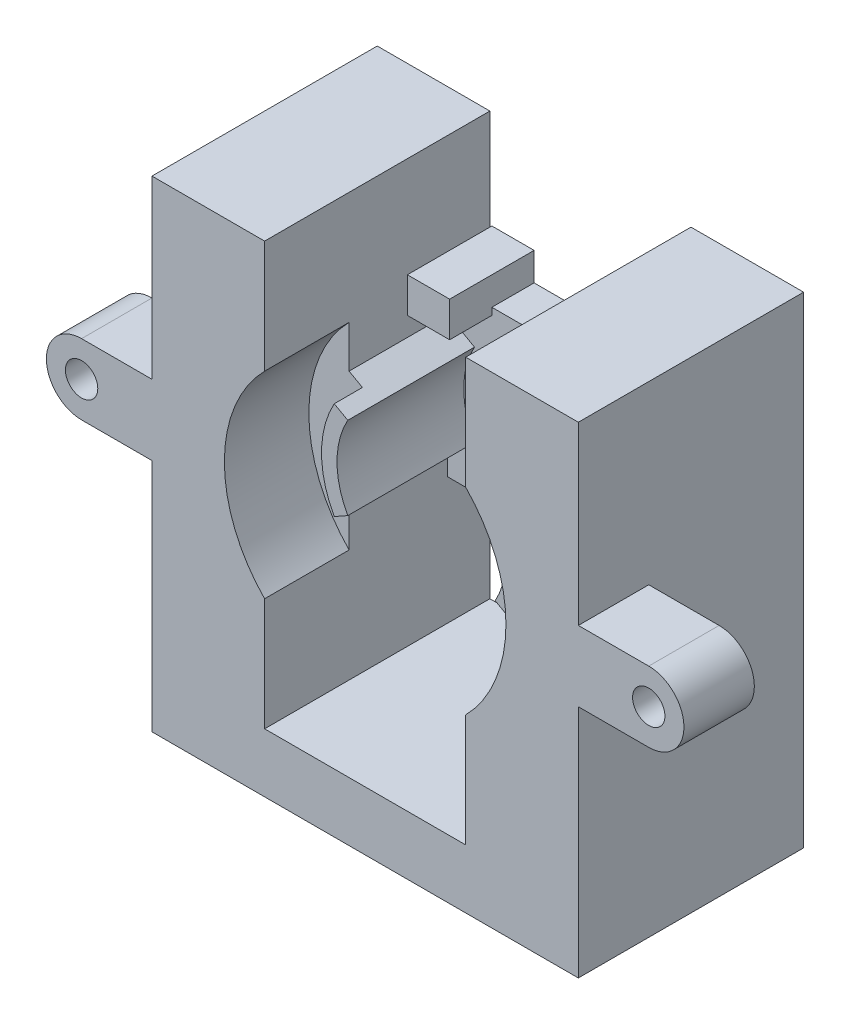
SolidWorks part; units mm, degrees
ref_plane "前视基准面" through (0, 0, 0) normal (0, 0, 1) x (1, 0, 0)
ref_plane "上视基准面" through (0, 0, 0) normal (0, 1, 0) x (1, 0, 0)
ref_plane "右视基准面" through (0, 0, 0) normal (1, 0, 0) x (0, 0, -1)
sketch "草图1" plane through (0, 0, 0) normal (0, 0, 1) x (1, 0, 0)
  line L0 (7.1414, 7) -> (7.1414, 15)
  line L1 (7.1414, 15) -> (15.1414, 15)
  line L2 (15.1414, 15) -> (15.1414, -19.186)
  line L3 (7.1414, -7) -> (7.1414, -15)
  line L4 (0, -293.0825) -> (0, 14343.5987) construction
  line L5 (4, 0) -> (4, -15) construction
  line L6 (4, -15) -> (7.1414, -15)
  line L7 (-4, 0) -> (-4, -15) construction
  line L8 (-4, -15) -> (-7.1414, -15)
  line L9 (-7.1414, -7) -> (-7.1414, -15)
  line L10 (-15.1414, 15) -> (-15.1414, -19.186)
  line L11 (-7.1414, 15) -> (-15.1414, 15)
  line L12 (-7.1414, 7) -> (-7.1414, 15)
  line L13 (-15.1414, -19.186) -> (15.1414, -19.186)
  line L14 (-4, -15) -> (4, -15)
  line L15 (7.1414, 7) -> (7.1414, 4)
  line L16 (7.1414, 4) -> (5.2348, 2.9321)
  line L17 (-1000, 0) -> (49000, 0) construction
  line L18 (7.1414, -4) -> (5.2348, -2.9321)
  line L19 (7.1414, -7) -> (7.1414, -4)
  line L20 (-7.1414, -7) -> (-7.1414, -4)
  line L21 (-7.1414, -4) -> (-5.2348, -2.9321)
  line L22 (-7.1414, 4) -> (-5.2348, 2.9321)
  line L23 (-7.1414, 7) -> (-7.1414, 4)
  line L24 (20.1414, 2.5) -> (15.1414, 2.5)
  line L25 (20.1414, -2.5) -> (15.1414, -2.5)
  line L26 (-20.1414, -2.5) -> (-15.1414, -2.5)
  line L27 (-20.1414, 2.5) -> (-15.1414, 2.5)
  line L28 (-7.1414, 6) -> (7.1414, 6)
  line L29 (-7.1414, -6) -> (7.1414, -6)
  circle A0 centre (0, 0) radius 4 construction
  circle A1 centre (0, 0) radius 10 construction
  circle A2 centre (0, 0) radius 2.6
  arc A3 (7.1414, 7) -> (7.1414, -7) centre (0, 0) cw
  arc A4 (-7.1414, 7) -> (-7.1414, -7) centre (0, 0) ccw
  circle A6 centre (0, 0) radius 6 construction
  circle A7 centre (0, 0) radius 7.1 construction
  arc A8 (5.2348, 2.9321) -> (5.2348, -2.9321) centre (0, 0) cw
  arc A9 (6.1945, 3.4696) -> (6.1945, -3.4696) centre (0, 0) cw
  arc A10 (-5.2348, 2.9321) -> (-5.2348, -2.9321) centre (0, 0) ccw
  arc A11 (-6.1945, 3.4696) -> (-6.1945, -3.4696) centre (0, 0) ccw
  circle A12 centre (20.1414, 0) radius 1.15
  circle A13 centre (20.1414, 0) radius 2.5 construction
  arc A14 (20.1414, 2.5) -> (20.1414, -2.5) centre (20.1414, 0) cw
  circle A15 centre (-20.1414, 0) radius 1.15
  arc A16 (-20.1414, 2.5) -> (-20.1414, -2.5) centre (-20.1414, 0) ccw
  dimension "D2" = 5.2
  dimension "D3" = 8
  dimension "D4" = 10
  dimension "D9" = 14.2
  dimension "D10" = 12
  dimension "D12" = 2.3
  dimension "D13" = 5
  dimension "D1" = 15
  dimension "D5" = 8
  dimension "D6" = 8
  dimension "D7" = 34.186
  dimension "D8" = 8
  dimension "D11" = 3
  dimension "D14" = 5
  dimension "D15" = 6
extrude "凸台-拉伸2" add sketch "草图1" along normal blind 16 contours A4 L12 L11 L10 L13 L2 L1 L0 A3 L3 L6 L14 L8 L9 | A11 L22 L23 A4 L20 L21 | L22 A11 L21 A10 | A9 L16 A8 L18 | L16 A9 L18 L19 A3 L15 region at (8.1661, 0, 0) region at (7.5981, 11, 0) region at (-8.1661, 0, 0) region at (6.2838, 0, 0) region at (-6.2838, 0, 0)
extrude "凸台-拉伸3" add sketch "草图1<3>" along normal blind 3 contours L22 A10 L21 L18 A8 L16 A2 region at (6.9549, 5, 0)
sketch "草图1<3>" plane through (0, 0, 0) normal (0, 0, 1) x (1, 0, 0) same geometry as "草图1"
extrude "凸台-拉伸4" add sketch "草图1<6>" against normal blind 5 from surface contours L27 A16 L26 L10 A15 | A14 L24 L2 L25 A12 region at (18.4428, 0, 0) region at (-18.4428, 0, 0) starting at face at (0, -0.5233, 16)
sketch "草图1<6>" plane through (0, 0, 0) normal (0, 0, 1) x (1, 0, 0) same geometry as "草图1"
extrude "切除-拉伸1" cut sketch "草图1<4>" along normal blind 13 from offset 10 contours A11 L22 L23 A4 L20 L21 | L16 A9 L18 L19 A3 L15 region at (8.1661, 0, 0) region at (-8.1661, 0, 0)
sketch "草图1<4>" plane through (0, 0, 0) normal (0, 0, 1) x (1, 0, 0) same geometry as "草图1"
extrude "切除-拉伸2" cut sketch "草图1<5>" along normal blind 13 from offset 12 contours L22 A11 L21 A10 | A9 L16 A8 L18 region at (6.2838, 0, 0) region at (-6.2838, 0, 0)
sketch "草图1<5>" plane through (0, 0, 0) normal (0, 0, 1) x (1, 0, 0) same geometry as "草图1"
sketch "草图3" plane through (0, 0, 0) normal (0, 0, -1) x (-1, 0, 0)
  circle A0 centre (0, 6) radius 1.05
  point P12 (2.0269, 12.75)
  point P13 (0, 0)
  point P14 (0, 12.75)
  point P15 (0.0669, 12.75)
  dimension "D2" = 2.1
  dimension "D1" = 6
extrude "凸台-拉伸5" add sketch "草图3" against normal blind 6
sketch "草图4" plane through (0, 0, 3) normal (0, 0, 1) x (1, 0, 0)
  line L0 (4, 5.5) -> (4, 8)
  line L2 (4, 8) -> (7, 8)
  line L3 (7, 8) -> (7, 5.5)
  line L4 (0, 0) -> (0, 10.3743) construction
  line L5 (-7, 8) -> (-7, 5.5)
  line L6 (-4, 8) -> (-7, 8)
  line L7 (-4, 5.5) -> (-4, 8)
  line L8 (-7, 5.5) -> (-4, 5.5)
  line L9 (4, 5.5) -> (7, 5.5)
  line L10 (-7.1414, 6) -> (-1.05, 6) construction
  dimension "D1" = 2
  dimension "D2" = 3
  dimension "D3" = 8
  dimension "D4" = 0.5
extrude "凸台-拉伸7" add sketch "草图4" along normal blind 6 from surface starting at face at (0, -10.5, 0)
